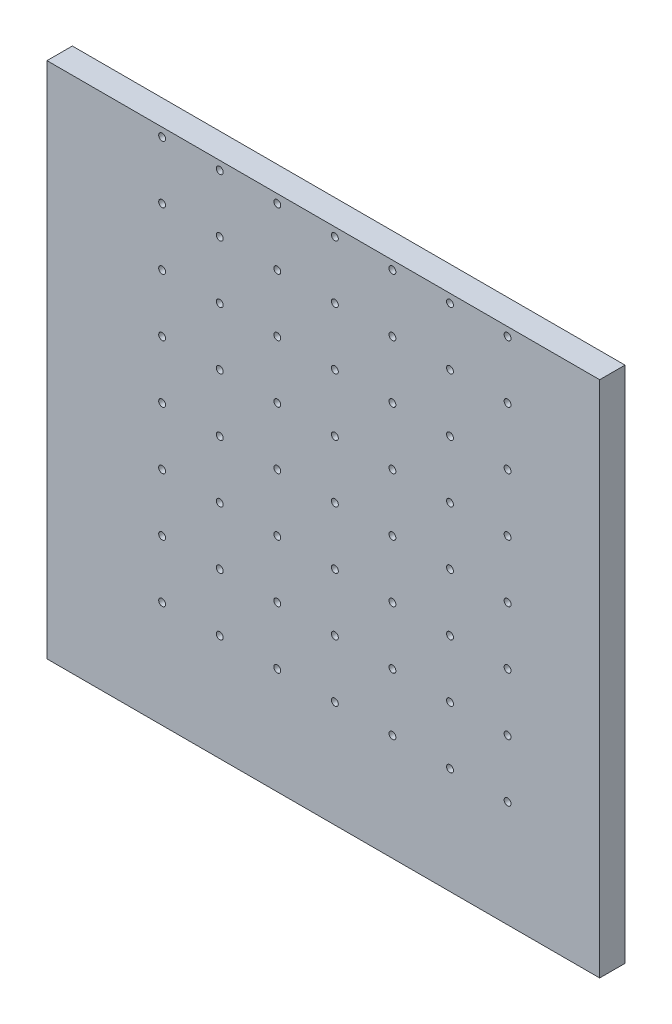
SolidWorks part; units mm, degrees
ref_plane "Front" through (0, 0, 0) normal (0, 0, 1) x (1, 0, 0)
ref_plane "Top" through (0, 0, 0) normal (0, 1, 0) x (1, 0, 0)
ref_plane "Right" through (0, 0, 0) normal (1, 0, 0) x (0, 0, -1)
sketch "Esquisse1" plane through (0, 0, 0) normal (0, 0, 1) x (1, 0, 0)
  line L1 (0, 0) -> (480, 0)
  line L2 (0, 0) -> (0, 450)
  line L3 (0, 450) -> (480, 450)
  line L4 (480, 0) -> (480, 450)
  dimension "D1" = 480
  dimension "D2" = 450
extrude "Boss.-Extru.1" add sketch "Esquisse1" along normal blind 22
sketch "Esquisse2" plane through (0, 0, 22) normal (0, 0, 1) x (1, 0, 0)
  line L0 (220, 135) -> (220, 45) construction
  line L1 (65, 400) -> (375, 400)
  line L2 (65, 400) -> (65, 135)
  line L3 (65, 135) -> (375, 135)
  line L4 (375, 400) -> (375, 135)
  line L5 (0, 0) -> (480, 0) construction
  line L6 (0, 450) -> (0, 0) construction
  line L7 (480, 450) -> (0, 450) construction
  line L8 (480, 0) -> (480, 450) construction
  dimension "D1" = 135
  dimension "D2" = 65
  dimension "D3" = 50
  dimension "D4" = 105
extrude "Enlèv. mat.-Extru.1" cut sketch "Esquisse2" along normal blind 1 from vertex starting at point (0, 450, 0)
sketch "Esquisse3" plane through (0, 0, 0) normal (0, 0, -1) x (-1, 0, 0)
  line L3 (-375, 267.5) -> (-65, 267.5) construction
  line L4 (-375, 135) -> (-375, 400) construction
  line L5 (-65, 400) -> (-65, 135) construction
  line L6 (-325, 267.5) -> (-325, 281.622) construction
  line L7 (-160, 267.5) -> (-160, 281.622) construction
  line L8 (-250, 317.5) -> (-255.5628, 317.5) construction
  line L9 (-160, 367.5) -> (-160, 353.378) construction
  line L10 (-325, 367.5) -> (-325, 353.378) construction
  line L11 (-375, 367.5) -> (-65, 367.5) construction
  line L16 (-314.1888, 417.5) -> (-265.4372, 417.5) construction
  line L17 (-480, 0) -> (-480, 450) construction
  line L18 (0, 0) -> (-480, 0) construction
  circle A0 centre (-400, 292.5) radius 3
  circle A1 centre (-350, 292.5) radius 3
  circle A2 centre (-150, 92.5) radius 3
  circle A3 centre (-100, 92.5) radius 3
  circle A4 centre (-200, 92.5) radius 3
  circle A5 centre (-300, 92.5) radius 3
  circle A6 centre (-300, 292.5) radius 3
  circle A7 centre (-250, 292.5) radius 3
  circle A8 centre (-200, 292.5) radius 3
  circle A9 centre (-250, 92.5) radius 3
  circle A10 centre (-400, 92.5) radius 3
  circle A11 centre (-350, 92.5) radius 3
  circle A12 centre (-150, 292.5) radius 3
  circle A13 centre (-100, 292.5) radius 3
  circle A14 centre (-100, 342.5) radius 3
  circle A15 centre (-150, 342.5) radius 3
  circle A16 centre (-150, 392.5) radius 3
  circle A17 centre (-100, 392.5) radius 3
  circle A18 centre (-200, 392.5) radius 3
  circle A19 centre (-200, 342.5) radius 3
  circle A20 centre (-250, 342.5) radius 3
  circle A21 centre (-300, 342.5) radius 3
  circle A22 centre (-300, 392.5) radius 3
  circle A23 centre (-250, 392.5) radius 3
  circle A24 centre (-400, 392.5) radius 3
  circle A25 centre (-350, 392.5) radius 3
  circle A26 centre (-350, 342.5) radius 3
  circle A27 centre (-400, 342.5) radius 3
  circle A28 centre (-400, 192.5) radius 3
  circle A29 centre (-350, 192.5) radius 3
  circle A30 centre (-350, 142.5) radius 3
  circle A31 centre (-400, 142.5) radius 3
  circle A32 centre (-250, 142.5) radius 3
  circle A33 centre (-300, 142.5) radius 3
  circle A34 centre (-300, 192.5) radius 3
  circle A35 centre (-250, 192.5) radius 3
  circle A36 centre (-200, 192.5) radius 3
  circle A37 centre (-200, 142.5) radius 3
  circle A38 centre (-100, 142.5) radius 3
  circle A39 centre (-150, 142.5) radius 3
  circle A40 centre (-150, 192.5) radius 3
  circle A41 centre (-100, 192.5) radius 3
  circle A42 centre (-100, 242.5) radius 3
  circle A43 centre (-150, 242.5) radius 3
  circle A44 centre (-200, 242.5) radius 3
  circle A45 centre (-250, 242.5) radius 3
  circle A46 centre (-300, 242.5) radius 3
  circle A47 centre (-350, 242.5) radius 3
  circle A48 centre (-400, 242.5) radius 3
  circle A49 centre (-350, 442.5) radius 3
  circle A50 centre (-400, 442.5) radius 3
  circle A51 centre (-250, 442.5) radius 3
  circle A52 centre (-300, 442.5) radius 3
  circle A53 centre (-200, 442.5) radius 3
  circle A54 centre (-100, 442.5) radius 3
  circle A55 centre (-150, 442.5) radius 3
  dimension "D1" = 6
  dimension "D3" = 25
  dimension "D4" = 50
  dimension "D5" = 50
  dimension "D6" = 50
  dimension "D9" = 175
  dimension "D11" = 225
  dimension "D12" = 275
  dimension "D13" = 25
  dimension "D15" = 125
extrude "Enlèv. mat.-Extru.2" cut sketch "Esquisse3" against normal through all
